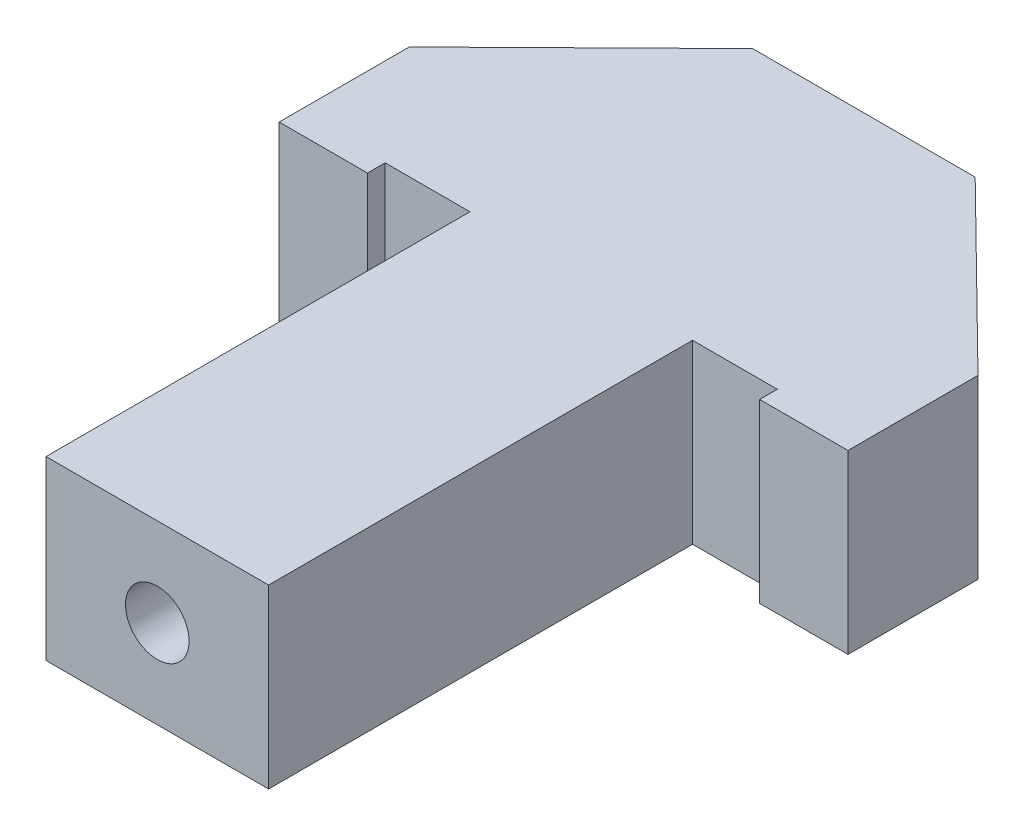
SolidWorks part; units mm, degrees
material "AISI 304"
ref_plane "Front Plane" through (0, 0, 0) normal (0, 0, 1) x (1, 0, 0)
ref_plane "Top Plane" through (0, 0, 0) normal (0, 1, 0) x (1, 0, 0)
ref_plane "Right Plane" through (0, 0, 0) normal (1, 0, 0) x (0, 0, -1)
sketch "Sketch1" plane through (0, 0, 0) normal (0, 1, 0) x (1, 0, 0)
  line L3 (0, 0) -> (4.1323, 0)
  line L4 (0, 0) -> (-2.0907, 0)
  line L5 (-2.0907, 0) -> (-2.0907, 4.0386)
  line L6 (-2.0907, 4.0386) -> (4.1323, 10.16)
  line L7 (4.1323, 10.16) -> (8.1328, 10.16)
  line L8 (8.1328, 10.16) -> (8.1328, -15.24)
  line L9 (4.1323, 0) -> (4.1323, -15.24)
  line L18 (4.1323, -15.24) -> (8.1328, -15.24)
  point P1 (0, 0)
  dimension "D1" = 4.0005
  dimension "D2" = 15.24
  dimension "D3" = 6.223
  dimension "D6" = 4.0005
  dimension "D7" = 25.4
  dimension "D8" = 4.0386
extrude "Boss-Extrude1" add sketch "Sketch1" along normal blind 6.35
ref_plane "Plane1" through (8.1328, 0, 0) normal (1, 0, 0) x (0, 0, -1)
mirror "Mirror1" about plane through (8.1328, 0, 0) normal (1, 0, 0) of "Boss-Extrude1"
sketch "Sketch3" plane through (0, 0, 0) normal (0, -1, 0) x (-1, 0, 0)
  line L0 (-18.3563, 0) -> (-12.1333, 0) construction
  line L1 (-15.1813, 0) -> (-18.3563, 0)
  line L2 (-15.1813, 0) -> (-15.1813, -0.635)
  line L3 (-15.1813, -0.635) -> (-18.3563, -0.635)
  line L4 (-18.3563, 0) -> (-18.3563, -0.635)
  dimension "D1" = 0.635
  dimension "D2" = 3.175
extrude "Boss-Extrude2" add sketch "Sketch3" against normal up to surface (6.35 mm away) up to face at (8.1328, 6.35, 0.2083)
mirror "Mirror2" about plane through (8.1328, 0, 0) normal (1, 0, 0) of "Boss-Extrude2"
sketch "Sketch4" plane through (0, 0, -10.16) normal (0, 0, -1) x (-1, 0, 0)
  line L0 (-12.1333, 0) -> (-4.1323, 0) construction
  line L1 (-12.1333, 6.35) -> (-12.1333, 0) construction
  circle A0 centre (-8.1328, 3.175) radius 1.143
  dimension "D1" = 2.286
  dimension "D2" = 3.175
  dimension "D3" = 4.0005
extrude "Cut-Extrude1" cut sketch "Sketch4" against normal blind 50.8
